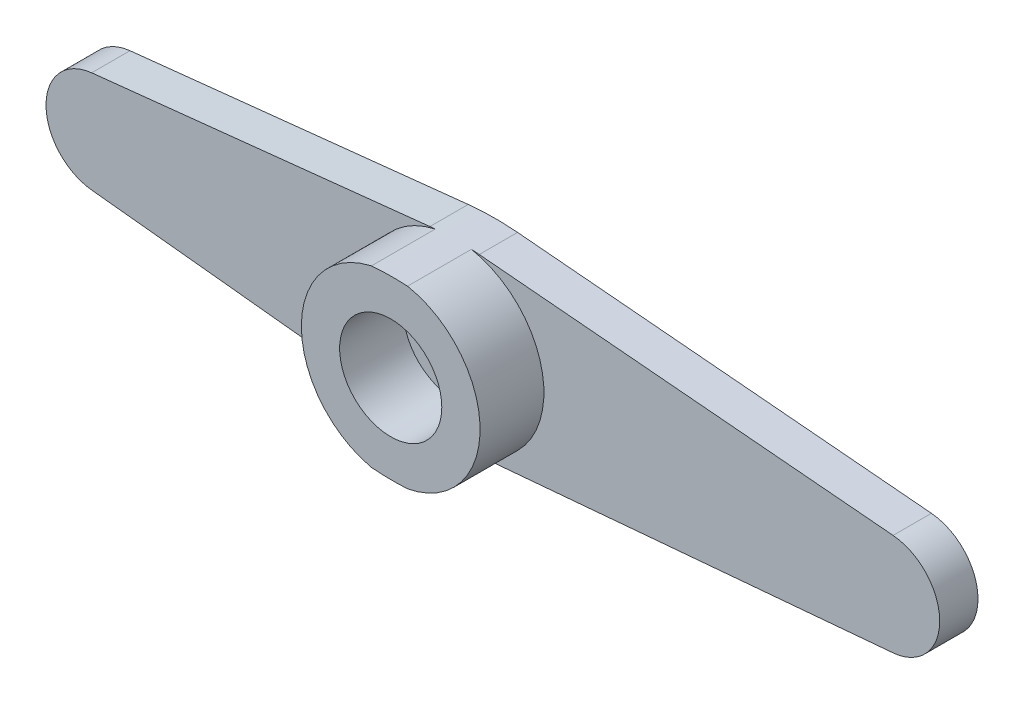
SolidWorks part; units mm, degrees
ref_plane "Front Plane" through (0, 0, 0) normal (0, 0, 1) x (1, 0, 0)
ref_plane "Top Plane" through (0, 0, 0) normal (0, 1, 0) x (1, 0, 0)
ref_plane "Right Plane" through (0, 0, 0) normal (1, 0, 0) x (0, 0, -1)
sketch "Sketch1" plane through (0, 0, 0) normal (0, 0, 1) x (1, 0, 0)
  line L0 (100, 0) -> (-100, 0) construction
  line L1 (100, -7.5) -> (-100, -7.5)
  line L2 (100, 7.5) -> (-100, 7.5)
  line L3 (0, 7.5) -> (0, -7.5) construction
  line L4 (-0.9651, 3.3974) -> (-14.2115, 1.9888)
  line L9 (0.9668, 3.4151) -> (17.1749, 1.9923)
  line L10 (0.9668, -3.4151) -> (17.1749, -1.9923)
  line L11 (-0.9651, -3.3974) -> (-14.2115, -1.9888)
  arc A0 (100, -7.5) -> (100, 7.5) centre (100, 0) ccw
  arc A1 (-100, 7.5) -> (-100, -7.5) centre (-100, 0) ccw
  circle A2 centre (100, 0) radius 5
  circle A3 centre (-100, 0) radius 5
  arc A6 (0.9668, 3.4151) -> (-0.9651, 3.3974) centre (0.0923, -6.5466) ccw
  arc A7 (-0.9651, -3.3974) -> (0.9668, -3.4151) centre (0.0923, 6.5466) ccw
  arc A8 (-14.2115, 1.9888) -> (-14.2115, -1.9888) centre (-14, 0) ccw
  arc A9 (17.1749, 1.9923) -> (17.1749, -1.9923) centre (17, 0) cw
  circle A10 centre (0, 0) radius 3.5
  circle A11 centre (0, 0) radius 2
  point P2 (0, 0)
  point P14 (19, 0)
  point P15 (-14, 0)
  point P16 (0, 3.5)
  point P17 (0, -3.5)
  point P30 (0, 3.5)
  point P33 (0, -3.5)
  dimension "D2" = 10
  dimension "D8" = 2
  dimension "D9" = 2
  dimension "D10" = 10
  dimension "D11" = 7
  dimension "D12" = 4
  dimension "D1" = 200
  dimension "D3" = 15
  dimension "D4" = 19
  dimension "D5" = 14
  dimension "D6" = 3.5
  dimension "D7" = 3.5
extrude "Boss-Extrude1" add sketch "Sketch1" along normal blind 1.5 contours L10 A9 L9 A6 L4 A8 L11 A7
extrude "Boss-Extrude2" add sketch "Sketch1<3>" along normal blind 4 contours A6 A10 A7 A11 region at (-0.0473, 3.3541, 0)
sketch "Sketch1<3>" plane through (0, 0, 0) normal (0, 0, 1) x (1, 0, 0) same geometry as "Sketch1"
